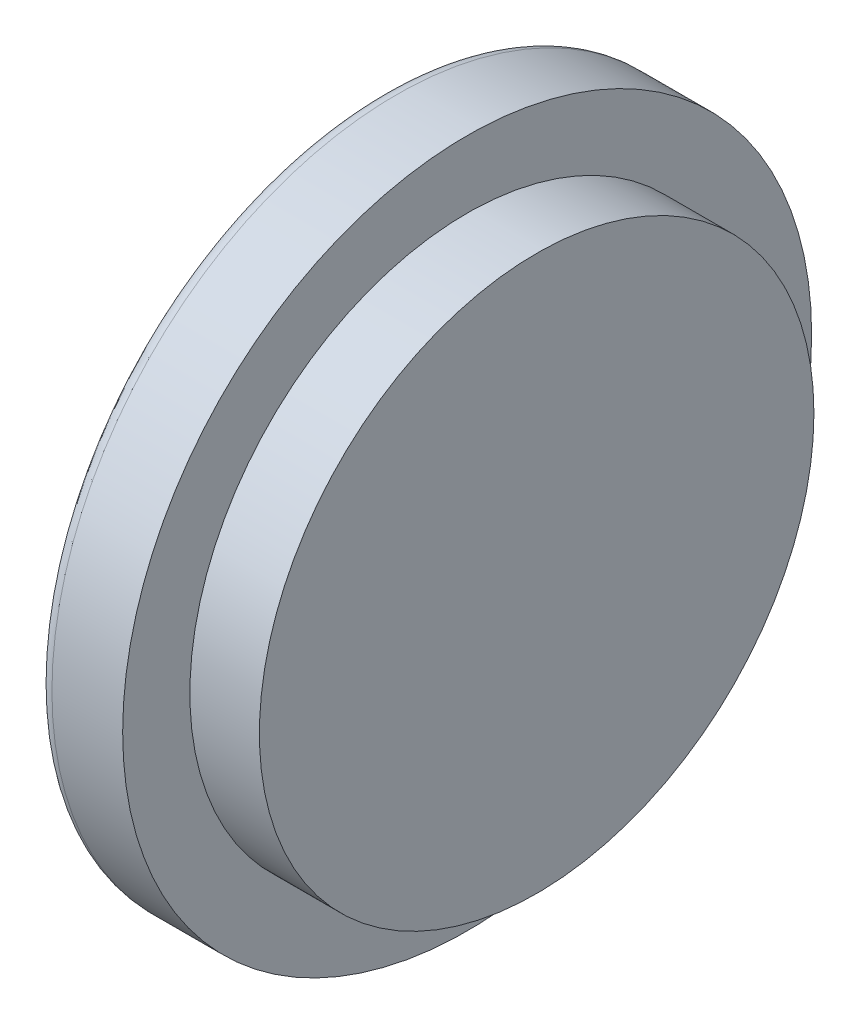
SolidWorks part; units mm, degrees
ref_plane "Front Plane" through (0, 0, 0) normal (0, 0, 1) x (1, 0, 0)
ref_plane "Top Plane" through (0, 0, 0) normal (0, 1, 0) x (1, 0, 0)
ref_plane "Right Plane" through (0, 0, 0) normal (1, 0, 0) x (0, 0, -1)
sketch "Sketch1" plane through (0, 0, 0) normal (1, 0, 0) x (0, 0, -1)
  circle A0 centre (0, 0) radius 154.627
  dimension "D1" = 309.254
extrude "Boss-Extrude1" add sketch "Sketch1" along normal blind 38.1
sketch "Sketch2" plane through (38.1, 0, 0) normal (1, 0, 0) x (0, 0, -1)
  circle A1 centre (0, 0) radius 124.46
extrude "Boss-Extrude2" add sketch "Sketch2" along normal blind 69.3 from surface starting at face at (0, 0, -154.627)
sketch "Sketch3" plane through (0, 0, 0) normal (-1, 0, 0) x (0, 0, 1)
  circle A0 centre (0, 0) radius 139.7
extrude "Cut-Extrude1" cut sketch "Sketch3" against normal blind 6.35
fillet "Fillet1" radius 6.35 1 edges at (0, 0, -154.627)
